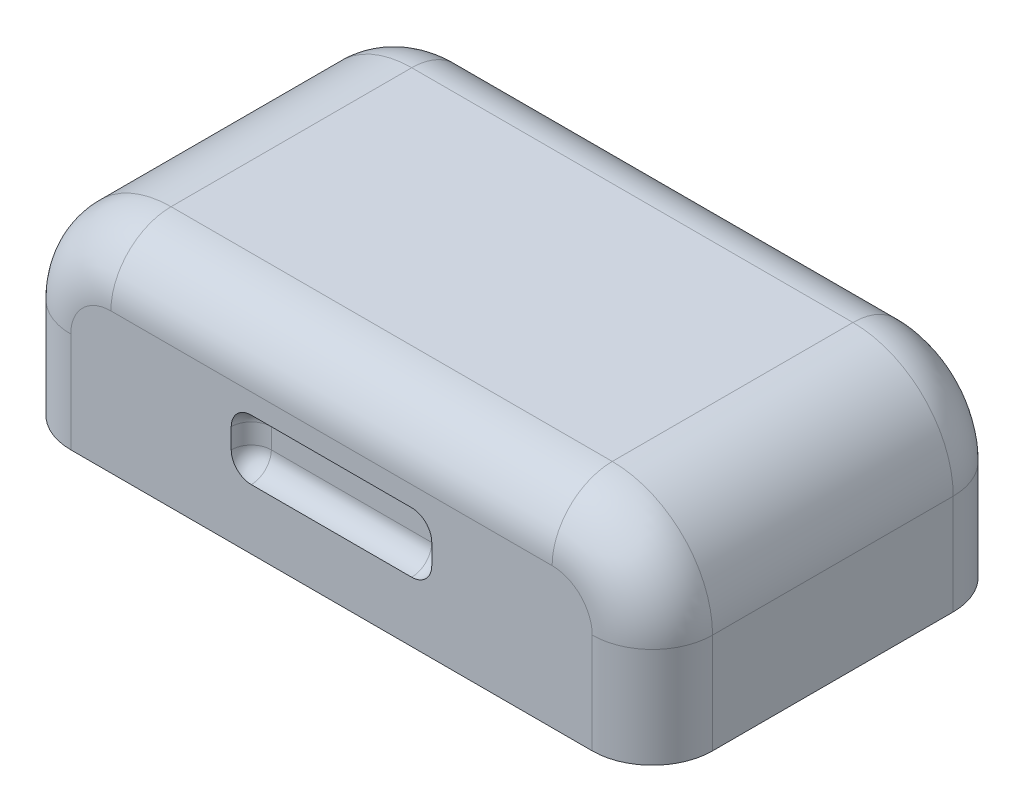
SolidWorks part; units mm, degrees
ref_plane "Plan de face" through (0, 0, 0) normal (0, 0, 1) x (1, 0, 0)
ref_plane "Plan de dessus" through (0, 0, 0) normal (0, 1, 0) x (1, 0, 0)
ref_plane "Plan de droite" through (0, 0, 0) normal (1, 0, 0) x (0, 0, -1)
sketch "Esquisse1" plane through (0, 0, 0) normal (0, 1, 0) x (1, 0, 0)
  line L1 (-44.6588, 68.7058) -> (115.3412, 68.7058)
  line L2 (-44.6588, 68.7058) -> (-44.6588, -21.2942)
  line L3 (-44.6588, -21.2942) -> (115.3412, -21.2942)
  line L4 (115.3412, 68.7058) -> (115.3412, -21.2942)
  dimension "D1" = 90
  dimension "D2" = 160
extrude "Extrusion1" add sketch "Esquisse1" along normal blind 50
fillet "Congé1" radius 25 2 edges at (-44.6588, 50, -23.7058) (115.3412, 50, -23.7058)
fillet "Congé2" radius 15 10 edges at (115.3412, 12.5, 21.2942) (108.0189, 42.6777, 21.2942) (35.3412, 50, 21.2942) (-37.3364, 42.6777, 21.2942) (-44.6588, 12.5, -68.7058) (-37.3364, 42.6777, -68.7058) (35.3412, 50, -68.7058) (108.0189, 42.6777, -68.7058) (-44.6588, 12.5, 21.2942) (115.3412, 12.5, -68.7058)
shell "Coque1" thickness 7 removed face at (35.3412, 0, -23.7058)
sketch "Esquisse2" plane through (0, 0, 21.2942) normal (0, 0, 1) x (1, 0, 0)
  line L0 (-29.6588, 0) -> (100.3412, 0) construction
  line L1 (10.3412, 30) -> (60.3412, 30)
  line L2 (10.3412, 30) -> (10.3412, 15)
  line L3 (10.3412, 15) -> (60.3412, 15)
  line L4 (60.3412, 30) -> (60.3412, 15)
  line L6 (35.3412, 0) -> (35.3412, 35) construction
  line L7 (90.3412, 35) -> (-19.6588, 35) construction
  dimension "D1" = 50
  dimension "D2" = 15
  dimension "D3" = 15
  dimension "D4" = 25
extrude "Enlèv. mat.-Extru.1" cut sketch "Esquisse2" against normal blind 5
fillet "Congé4" radius 5 1 edges at (35.3412, 15, 16.2942) type face fillet first side face at (35.3412, 15, 18.7942) second side face at (35.3412, 22.5, 16.2942)
fillet "Congé5" radius 5 1 edges at (35.3412, 30, 16.2942) type face fillet first side face at (35.3412, 30, 18.7942) second side face at (35.3412, 25, 16.2942)
fillet "Congé6" radius 5 1 edges at (10.3412, 22.5, 16.2942) type face fillet first side face at (10.3412, 22.5, 18.2765) second side face at (35.3412, 22.5, 16.2942)
fillet "Congé7" radius 5 1 edges at (60.3412, 22.5, 16.2942) type face fillet first side face at (60.3412, 22.5, 18.2765) second side face at (37.8412, 22.5, 16.2942)
ref_plane "Plan1" through (0, 0, -23.7058) normal (0, 0, 1) x (1, 0, 0)
mirror "Symétrie1" about plane through (0, 0, -23.7058) normal (0, 0, 1) of "Congé7", "Congé6", "Congé5", "Congé4", "Enlèv. mat.-Extru.1"
scale "Echelle1" scale about centroid uniform scaling yes scale factor 1.125
